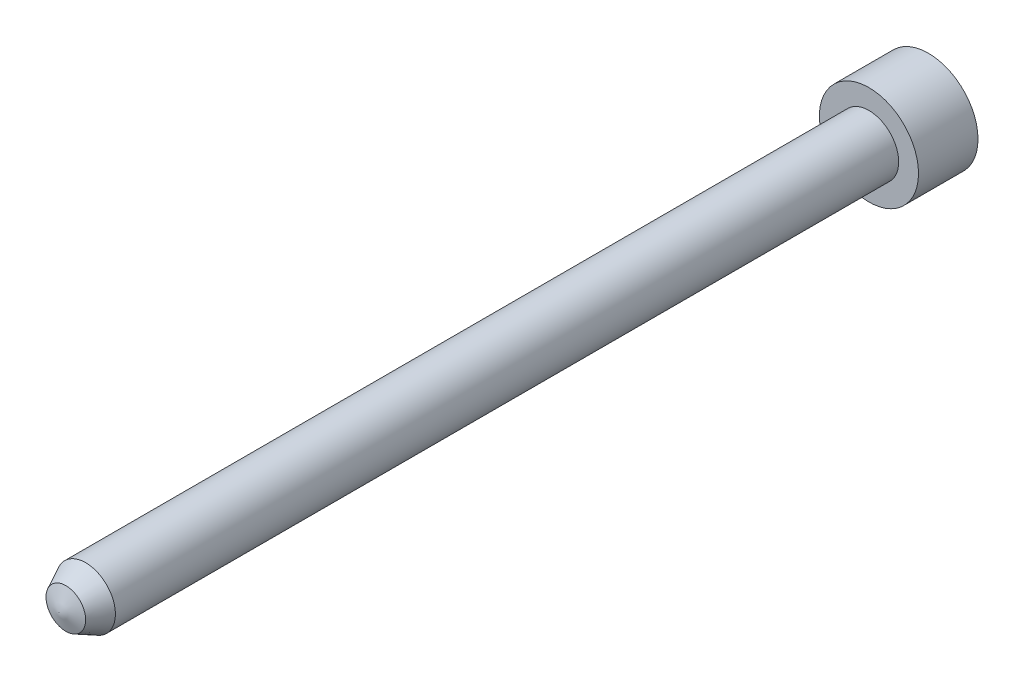
SolidWorks part; units mm, degrees
material "POM Acetal Copolymer"
ref_plane "Front Plane" through (0, 0, 0) normal (0, 0, 1) x (1, 0, 0)
ref_plane "Top Plane" through (0, 0, 0) normal (0, 1, 0) x (1, 0, 0)
ref_plane "Right Plane" through (0, 0, 0) normal (1, 0, 0) x (0, 0, -1)
sketch "Extrude sketch 1" plane through (0, 0, 0) normal (0, 0, 1) x (1, 0, 0)
  circle A0 centre (860, -225) radius 15
  dimension "D1" = 30
extrude "Extrude 1" add sketch "Extrude sketch 1" along normal blind 18 from offset 300 separate body
sketch "Extrude sketch 2" plane through (0, 0, 0) normal (0, 0, 1) x (1, 0, 0)
  circle A0 centre (860, -225) radius 9
  dimension "D1" = 18
extrude "Extrude 2" add sketch "Extrude sketch 2" along normal blind 237 from offset 318 separate body
ref_plane "Plane Y=-225" through (0, -225, 0) normal (0, 1, 0) x (1, 0, 0)
sketch "Revolve profile 1" plane through (0, -225, 0) normal (0, 1, 0) x (1, 0, 0)
  line L0 (860, -555) -> (869, -555)
  line L1 (869, -555) -> (866, -561)
  line L2 (866, -561) -> (860, -563)
  line L3 (860, -563) -> (860, -555)
  line L4 (860, -550) -> (860, -568) construction
  dimension "D1" = 6
  dimension "D2" = 9
  dimension "D3" = 6
  dimension "D4" = 8
revolve "Revolve 1" add sketch "Revolve profile 1" angle 360 about L4
combine bodies "Combine (weld / assembly of features)" operation type add bodies to combine 101 102 103
